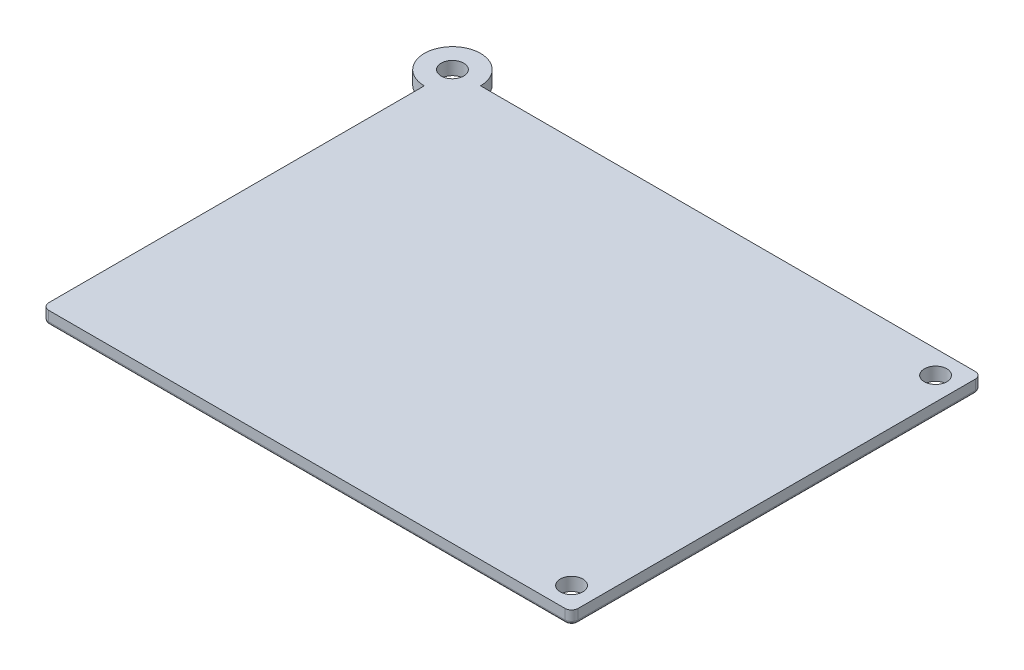
SolidWorks part; units mm, degrees
material "PVC Rigid"
ref_plane "Front Plane" through (0, 0, 0) normal (0, 0, 1) x (1, 0, 0)
ref_plane "Top Plane" through (0, 0, 0) normal (0, 1, 0) x (1, 0, 0)
ref_plane "Right Plane" through (0, 0, 0) normal (1, 0, 0) x (0, 0, -1)
sketch "Sketch1" plane through (0, 0, 0) normal (0, 1, 0) x (1, 0, 0)
  line L0 (40, -31) -> (-40, 31) construction
  line L1 (-40, -31) -> (40, -31)
  line L2 (-40, -31) -> (-40, 26.75)
  line L3 (-35.75, 31) -> (40, 31)
  line L4 (40, -31) -> (40, 31)
  line L5 (-40, -31) -> (40, 31) construction
  arc A5 (-35.75, 31) -> (-40, 26.75) centre (-40, 31) ccw
  point P0 (0, 0)
  dimension "D3" = 4.25
  dimension "D4" = 4.25
  dimension "D5" = 4.25
  dimension "D1" = 80
  dimension "D2" = 62
extrude "Main Body" add sketch "Sketch1" along normal blind 2
fillet "Corners" radius 1 3 edges at (-40, 1, 31) (40, 1, -31) (40, 1, 31)
fillet "Edge" radius 0.5 7 edges at (-39.7071, 0, 30.7071) (39.7071, 0, -30.7071) (39.7071, 0, 30.7071) (-40, 0, 1.625) (1.625, 0, -31) (40, 0, 0) (0, 0, 31)
sketch "Sketch7" plane through (0, 0, 0) normal (0, -1, 0) x (-1, 0, 0)
  line L0 (39, -31) -> (-39, -31) construction
  line L3 (-40, -30) -> (-40, 30) construction
  line L4 (-39, 31) -> (35.75, 31) construction
  circle A0 centre (40, 31) radius 1.7
  circle A2 centre (-36.5, -27.5) radius 1.7
  circle A3 centre (-36.5, 27.5) radius 1.7
  arc A4 (39.5, 26.7795) -> (35.7795, 30.5) centre (40, 31) ccw construction
  dimension "D1" = 3.4
  dimension "D4" = 3.4
  dimension "D5" = 3.4
  dimension "D2" = 3.5
  dimension "D3" = 3.5
  dimension "D6" = 3.5
extrude "Lid Holes" cut sketch "Sketch7" against normal through all both and the other way through all
sketch "Sketch4" plane through (0, 0, 0) normal (0, -1, 0) x (-1, 0, 0)
  line L0 (-30, 24) -> (-30, -24) construction
  line L3 (-1.1, 0) -> (1.1, 0) construction
  line L4 (-40, -30) -> (-40, 30) construction
  circle A0 centre (-30, 24) radius 2.325
  circle A1 centre (-30, 16) radius 2.325
  point P2 (-30, 0)
  dimension "D1" = 4.65
  dimension "D2" = 4.65
  dimension "D3" = 8
  dimension "D4" = 48
  dimension "D5" = 10
extrude "Boss-Extrude3" add sketch "Sketch4" along normal blind 1.6
fillet "Fillet3" radius 0.05 1 edges at (30, -1.6, -26.325)
pattern_linear "LPattern5" count 4 spacing 8 along (-1, 0, 0) of "Boss-Extrude3", "Fillet3"
sketch "LEGO straightline reference" plane through (0, 0, 0) normal (0, -1, 0) x (-1, 0, 0)
  line L0 (-30, 24) -> (-30, 16) construction
  line L1 (-30, 16) -> (-30, 20) construction
  line L2 (-30, 20) -> (-6, 20) construction
  line L3 (-6, 24) -> (-6, 16) construction
  point P10 (-18, 20)
sketch "MOVE ME TO CHANGE PEG ANGLE" plane through (0, 0, 0) normal (0, -1, 0) x (-1, 0, 0)
  line L0 (39, -31) -> (-39, -31) construction
  line L2 (-28, -19) -> (-20.1183, -3.4035) construction
  line L3 (-40, -30) -> (-40, 30) construction
  point P0 (-28, -19)
  dimension "D1" = 12
  dimension "D2" = 12
sketch "Sketch9" plane through (0, 0, 0) normal (0, -1, 0) x (1, 0, 0)
  line L0 (31.57, 17.1959) -> (24.43, 20.8041) construction
  line L1 (28, 19) -> (22.5876, 8.2899) construction
  line L2 (28, 19) -> (20.1183, 3.4035) construction
  circle A0 centre (31.57, 17.1959) radius 2.325
  circle A1 centre (24.43, 20.8041) radius 2.325
  point P4 (28, 19)
  dimension "D1" = 4.65
  dimension "D2" = 4.65
  dimension "D3" = 8
  dimension "D4" = 12
extrude "LEGO Pegs" add sketch "Sketch9" along normal blind 1.6
fillet "Soften 3D printed corners" radius 0.05 2 edges at (24.43, -1.6, 18.4791) (31.57, -1.6, 14.8709)
pattern_linear "LPattern6" count 4 spacing 8 along (-0.451, 0, -0.8925) of "LEGO Pegs", "Soften 3D printed corners"
equation "\"D3@Sketch7\"=\"D2@Sketch7\""
equation "\"D4@Sketch7\"=\"D1@Sketch7\""
equation "\"D5@Sketch7\"=\"D1@Sketch7\""
equation "\"D2@Sketch4\"=\"D1@Sketch4\""
equation "\"D2@Sketch9\"=\"D1@Sketch9\""
equation "\"D2@MOVE ME TO CHANGE PEG ANGLE\"=\"D1@MOVE ME TO CHANGE PEG ANGLE\""
